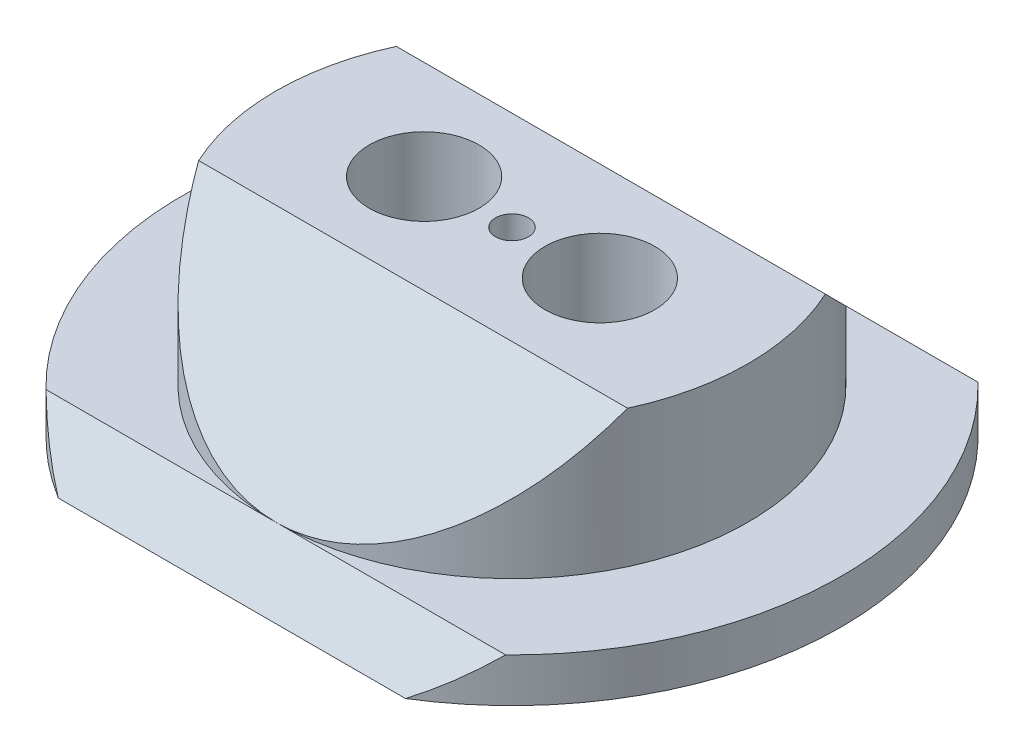
SolidWorks part; units mm, degrees
ref_plane "Front Plane" through (0, 0, 0) normal (0, 0, 1) x (1, 0, 0)
ref_plane "Top Plane" through (0, 0, 0) normal (0, 1, 0) x (1, 0, 0)
ref_plane "Right Plane" through (0, 0, 0) normal (1, 0, 0) x (0, 0, -1)
sketch "Sketch1" plane through (0, 0, 0) normal (0, 1, 0) x (1, 0, 0)
  circle A0 centre (0, 0) radius 30
extrude "Boss-Extrude1" add sketch "Sketch1" along normal blind 4
sketch "Sketch2" plane through (0, 0, 0) normal (1, 0, 0) x (0, 0, -1)
  line L0 (0, 4) -> (21.5, 4)
  line L1 (30, 4) -> (-30, 4) construction
  line L3 (0, 4) -> (-21.5, 4)
  line L5 (0, 4) -> (0, 19.5) construction
  line L6 (-9, 16.5) -> (-21.5, 4)
  line L7 (-9, 16.5) -> (9, 16.5)
  line L9 (9, 16.5) -> (21.5, 4)
  dimension "D1" = 12.5
  dimension "D2" = 45
  dimension "D3" = 21.5
  dimension "D4" = 21.5
  dimension "D5" = 45
sketch "Sketch3" plane through (0, 4, 0) normal (0, 1, 0) x (1, 0, 0)
  circle A0 centre (0, 0) radius 21.5
  dimension "D1" = 43
extrude "Boss-Extrude2" add sketch "Sketch2" along normal up to surface and the other way up to surface up to face at (0, 4, 30) other way up to face at (0, 4, 30)
ref_plane "Plane1" through (0, 12.75, -12.75) normal (0, 0.7071, -0.7071) x (1, 0, 0)
other "SurfaceCut1" flip cut yes
ref_plane "Plane2" through (0, 12.75, 12.75) normal (0, 0.7071, 0.7071) x (1, 0, 0)
other "SurfaceCut2" flip cut yes
extrude "Cut-Extrude2" cut sketch "Sketch3" against normal up to surface (12.5 mm away) flip side to cut contours A0
sketch "Sketch5" plane through (0, 0, 0) normal (0, -1, 0) x (-1, 0, 0)
  line L0 (0, 0) -> (0, -6)
  line L1 (0, -6) -> (-17.5, -6)
  line L2 (-17.5, -6) -> (-17.5, 6)
  line L3 (-17.5, 6) -> (17.5, 6)
  line L4 (17.5, 6) -> (17.5, -6)
  line L5 (17.5, -6) -> (0, -6)
  circle A0 centre (0, 0) radius 6
  circle A1 centre (0, 0) radius 3.5
  dimension "D1" = 12
  dimension "D2" = 7
  dimension "D3" = 12
  dimension "D4" = 6
  dimension "D5" = 35
  dimension "D6" = 17.5
extrude "Boss-Extrude3" add sketch "Sketch5" along normal blind 18 contours L1 L2 L3 L4 L5
sketch "Sketch6" plane through (0, 0, 0) normal (0, -1, 0) x (1, 0, 0)
  line L0 (0, 6) -> (0, 15) construction
  line L1 (-17.5, 6) -> (17.5, 6) construction
  line L2 (0, 15) -> (7, 15)
  line L3 (7, 15) -> (7, 6)
  line L4 (-17.5, 6) -> (17.5, 6) construction
  line L5 (7, 6) -> (-7, 6)
  line L6 (-7, 6) -> (-7, 15)
  line L7 (-7, 15) -> (0, 15)
  dimension "D1" = 14
  dimension "D2" = 9
extrude "Boss-Extrude4" add sketch "Sketch6" along normal blind 15 contours L7 L2 L3 L5 L6
sketch "Sketch7" plane through (0, 0, 0) normal (0, -1, 0) x (1, 0, 0)
  line L0 (0, -6) -> (0, -15) construction
  line L1 (17.5, -6) -> (-17.5, -6) construction
  line L2 (0, -15) -> (7, -15)
  line L3 (7, -15) -> (7, -6)
  line L4 (7, -6) -> (-7, -6)
  line L7 (-7, -6) -> (-7, -15)
  line L8 (-7, -15) -> (0, -15)
  dimension "D1" = 9
  dimension "D2" = 14
extrude "Boss-Extrude5" add sketch "Sketch7" along normal blind 15
sketch "Sketch8" plane through (0, 0, 0) normal (0, 0, 1) x (1, 0, 0)
  line L0 (0, 0) -> (12.5, 0) construction
  line L1 (12.5, 0) -> (12.5, -12.5) construction
  line L2 (12.5, -12.5) -> (-12.5, -12.5) construction
  line L3 (-12.5, -12.5) -> (-12.5, 0) construction
  line L4 (-12.5, 0) -> (0, 0) construction
  circle A0 centre (-12.5, -12.5) radius 2
  circle A1 centre (12.5, -12.5) radius 2
  dimension "D4" = 4
  dimension "D5" = 4
  dimension "D1" = 12.5
  dimension "D2" = 25
  dimension "D3" = 12.5
extrude "Cut-Extrude3" cut sketch "Sketch8" against normal through all both and the other way through all contours A0 | A1
ref_plane "Plane3" through (0, -18, 0) normal (0, -1, 0) x (-1, 0, 0)
ref_plane "Plane4" through (10.366, -9.6749, -8.0624) normal (0.6355, -0.5931, -0.4943) x (-0.3613, 0.3373, -0.8693)
ref_plane "Plane5" through (-10.366, -9.6749, -8.0624) normal (0.6355, 0.5931, 0.4943) x (0.3613, 0.3373, -0.8693)
ref_plane "Plane6" through (10.366, -9.6749, 8.0624) normal (-0.6355, 0.5931, -0.4943) x (-0.3613, 0.3373, 0.8693)
ref_plane "Plane7" through (-10.366, -9.6749, 8.0624) normal (0.6355, 0.5931, -0.4943) x (-0.3613, -0.3373, -0.8693)
ref_plane "Plane9" through (0, 0, 6) normal (0, 0, 1) x (1, 0, 0)
sketch "Sketch16" plane through (0, 0, 6) normal (0, 0, 1) x (1, 0, 0)
  line L0 (17.5, -18) -> (17.5, -14.5)
  line L1 (-6.6, -18) -> (6.6, -18) construction
  line L2 (17.5, -18) -> (17.5, 0) construction
  line L3 (17.5, -18) -> (14, -18)
  line L4 (17.5, -14.5) -> (14, -18)
  line L5 (-17.5, -18) -> (-14, -18)
  line L6 (-17.5, -18) -> (-17.5, 0) construction
  line L7 (-14, -18) -> (-17.5, -14.5)
  line L8 (-17.5, -14.5) -> (-17.5, -18)
  dimension "D2" = 3.5
extrude "Cut-Extrude8" cut sketch "Sketch16" against normal through all both and the other way through all
sketch "Sketch17" plane through (10.366, -9.6749, -8.0624) normal (0.6355, -0.5931, -0.4943) x (-0.3613, 0.3373, -0.8693)
  line L0 (-2.3725, -6.1896) -> (7.9806, -0.7067)
  line L1 (5.4512, -6.1896) -> (10.5101, 4.7762) construction
  line L2 (7.9806, -0.7067) -> (7.9806, -10.9658)
  line L3 (10.5101, -15.7421) -> (5.4512, -6.1896) construction
  line L4 (7.9806, -10.9658) -> (-2.3725, -6.1896)
extrude "Cut-Extrude9" cut sketch "Sketch17" along normal through all
sketch "Sketch19" plane through (-10.366, -9.6749, -8.0624) normal (0.6355, 0.5931, 0.4943) x (0.3613, 0.3373, -0.8693)
  line L0 (-2.3725, -6.1896) -> (7.9806, -10.9658)
  line L1 (7.9806, -10.9658) -> (7.9806, -0.7067)
  line L2 (5.4512, -6.1896) -> (10.5101, 4.7762) construction
  line L3 (7.9806, -0.7067) -> (-2.3725, -6.1896)
extrude "Cut-Extrude11" cut sketch "Sketch19" against normal blind 20 contours L3 L0 L1
sketch "Sketch20" plane through (-10.366, -9.6749, 8.0624) normal (0.6355, 0.5931, -0.4943) x (-0.3613, -0.3373, -0.8693)
  line L0 (2.3725, -6.1896) -> (-7.9806, -0.7067)
  line L1 (-5.4512, -6.1896) -> (-10.5101, 4.7762) construction
  line L2 (-7.9806, -0.7067) -> (-7.9806, -10.9658)
  line L3 (-5.4512, -6.1896) -> (-10.5101, -15.7421) construction
  line L4 (-7.9806, -10.9658) -> (2.3725, -6.1896)
extrude "Cut-Extrude12" cut sketch "Sketch20" against normal blind 20
sketch "Sketch21" plane through (10.366, -9.6749, 8.0624) normal (-0.6355, 0.5931, -0.4943) x (-0.3613, 0.3373, 0.8693)
  line L0 (-2.3725, -6.1896) -> (7.9806, -0.7067)
  line L1 (5.4512, -6.1896) -> (10.5101, 4.7762) construction
  line L2 (7.9806, -0.7067) -> (7.9806, -10.9658)
  line L3 (7.9806, -10.9658) -> (-2.3725, -6.1896)
extrude "Cut-Extrude13" cut sketch "Sketch21" against normal blind 20 contours L0 L2 L3
ref_plane "Plane10" through (0, 16.5, 0) normal (0, 1, 0) x (1, 0, 0)
sketch "Sketch25" plane through (0, 0, 0) normal (0, 0, 1) x (1, 0, 0)
  line L1 (-33.0377, 0) -> (33.0377, 0)
  line L2 (-33.0377, 0) -> (-33.0377, -20.1422)
  line L3 (-33.0377, -20.1422) -> (33.0377, -20.1422)
  line L4 (33.0377, 0) -> (33.0377, -20.1422)
  dimension "D1" = 20.1422
  dimension "D2" = 66.0754
extrude "Cut-Extrude14" cut sketch "Sketch25" along normal through all both and the other way through all
sketch "Sketch26" plane through (0, 16.5, 0) normal (0, 1, 0) x (1, 0, 0)
  line L0 (-9.1838, 0) -> (9.1838, 0) construction
  circle A0 centre (-8, 0) radius 5
  circle A2 centre (8, 0) radius 5
  dimension "D1" = 10
  dimension "D2" = 10
  dimension "D3" = 8
  dimension "D4" = 8
extrude "Cut-Extrude15" cut sketch "Sketch26" against normal blind 24
sketch "Sketch27" plane through (0, 16.5, 0) normal (0, 1, 0) x (1, 0, 0)
  line L0 (0, -9.1838) -> (0, 9.1838) construction
  circle A0 centre (0, 0) radius 1.5
  dimension "D1" = 3
  dimension "D2" = 0
extrude "Cut-Extrude16" cut sketch "Sketch27" against normal blind 30
sketch "Sketch28" plane through (0, 0, 0) normal (0, -1, 0) x (1, 0, 0)
  line L0 (0, -9.075) -> (0, 9.075) construction
  line L1 (9.075, 0) -> (-9.075, 0) construction
  circle A0 centre (0, -15) radius 5
  circle A1 centre (22, 0) radius 5
  circle A2 centre (0, 15) radius 5
  circle A3 centre (-22, 0) radius 5
  circle A4 centre (-14, 12) radius 5
  circle A5 centre (14, 12) radius 5
  circle A6 centre (14, -12) radius 5
  circle A7 centre (-14, -12) radius 5
  dimension "D1" = 10
  dimension "D2" = 10
  dimension "D3" = 10
  dimension "D4" = 10
  dimension "D5" = 10
  dimension "D6" = 10
  dimension "D7" = 10
  dimension "D10" = 10
  dimension "D11" = 15
  dimension "D8" = 22
  dimension "D9" = 22
  dimension "D12" = 15
  dimension "D13" = 14
  dimension "D14" = 14
  dimension "D15" = 14
  dimension "D16" = 14
  dimension "D17" = 12
  dimension "D18" = 12
  dimension "D19" = 12
  dimension "D20" = 12
extrude "Cut-Extrude17" cut sketch "Sketch28" against normal blind 3
